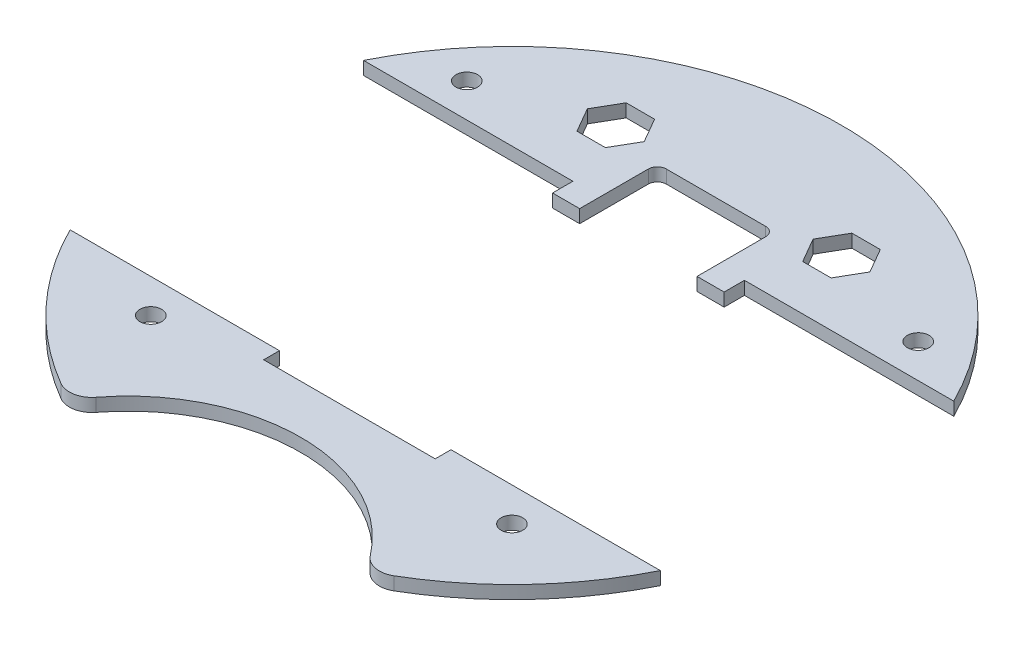
SolidWorks part; units mm, degrees
material "Acrylic (Medium-high impact)"
ref_plane "Front Plane" through (0, 0, 0) normal (0, 0, 1) x (1, 0, 0)
ref_plane "Top Plane" through (0, 0, 0) normal (0, 1, 0) x (1, 0, 0)
ref_plane "Right Plane" through (0, 0, 0) normal (1, 0, 0) x (0, 0, -1)
sketch "Sketch1" plane through (0, 0, 0) normal (0, 1, 0) x (1, 0, 0)
  line L0 (0, -85) -> (-32.7511, -65.2408) construction
  line L1 (0, -85) -> (0, 0) construction
  arc A0 (36.8566, -63.0126) -> (-36.8566, -63.0126) centre (0, 0) ccw
  arc A1 (30.3631, -61.7375) -> (-30.3631, -61.7375) centre (0, -85) ccw
  arc A2 (36.8566, -63.0126) -> (30.3631, -61.7375) centre (34.3322, -58.6967) cw
  arc A3 (-30.3631, -61.7375) -> (-36.8566, -63.0126) centre (-34.3322, -58.6967) cw
  dimension "D1" = 146
  dimension "D2" = 76.5
  dimension "D4" = 5
  dimension "D3" = 85
extrude "Boss-Extrude1" add sketch "Sketch1" along normal blind 2.9
sketch "solenoid placement" plane through (0, 2.9, 0) normal (0, 1, 0) x (1, 0, 0)
  line L4 (-19, -36) -> (19, -36)
  line L5 (-19, 28) -> (-19, -36)
  line L6 (19, 28) -> (-19, 28)
  line L7 (19, -36) -> (19, 28)
  line L8 (-19, -36) -> (19, -36)
  line L9 (-19, 28) -> (-19, -36)
  line L10 (19, 28) -> (-19, 28)
  line L11 (19, -36) -> (19, 28)
  dimension "D1" = 0
extrude "Cut-Extrude1" cut sketch "solenoid placement" against normal through all
sketch "Sketch5" plane through (0, 2.9, 0) normal (0, 1, 0) x (1, 0, 0)
  line L6 (-18.7069, 48) -> (-21.8534, 53.45)
  line L7 (-21.8534, 53.45) -> (-28.1466, 53.45)
  line L8 (-28.1466, 53.45) -> (-31.2931, 48)
  line L9 (-31.2931, 48) -> (-28.1466, 42.55)
  line L10 (-28.1466, 42.55) -> (-21.8534, 42.55)
  line L11 (-21.8534, 42.55) -> (-18.7069, 48)
  line L12 (-18.7069, 48) -> (-21.8534, 53.45)
  line L13 (-21.8534, 53.45) -> (-28.1466, 53.45)
  line L14 (-28.1466, 53.45) -> (-31.2931, 48)
  line L15 (-31.2931, 48) -> (-28.1466, 42.55)
  line L16 (-28.1466, 42.55) -> (-21.8534, 42.55)
  line L17 (-21.8534, 42.55) -> (-18.7069, 48)
  line L18 (18.7069, 48) -> (21.8534, 42.55)
  line L19 (21.8534, 53.45) -> (18.7069, 48)
  line L20 (28.1466, 53.45) -> (21.8534, 53.45)
  line L21 (31.2931, 48) -> (28.1466, 53.45)
  line L22 (28.1466, 42.55) -> (31.2931, 48)
  line L23 (21.8534, 42.55) -> (28.1466, 42.55)
  line L24 (18.7069, 48) -> (21.8534, 42.55)
  line L25 (21.8534, 53.45) -> (18.7069, 48)
  line L26 (28.1466, 53.45) -> (21.8534, 53.45)
  line L27 (31.2931, 48) -> (28.1466, 53.45)
  line L28 (28.1466, 42.55) -> (31.2931, 48)
  line L29 (21.8534, 42.55) -> (28.1466, 42.55)
  dimension "D1" = 0
  dimension "D2" = 0
extrude "Cut-Extrude5" cut sketch "Sketch5" against normal through all
sketch "Sketch6" plane through (0, 2.9, 0) normal (0, 1, 0) x (1, 0, 0)
  circle A1 centre (40, -40) radius 2.4
  circle A2 centre (40, -40) radius 2.4
  circle A3 centre (-40, -40) radius 2.4
  circle A4 centre (-40, -40) radius 2.4
  circle A5 centre (-50, 40) radius 2.4
  circle A6 centre (-50, 40) radius 2.4
  circle A7 centre (50, 40) radius 2.4
  circle A8 centre (50, 40) radius 2.4
  dimension "D1" = 0
  dimension "D2" = 0
  dimension "D3" = 0
  dimension "D4" = 0
extrude "Cut-Extrude6" cut sketch "Sketch6" against normal through all
sketch "Sketch3" plane through (0, 2.9, 0) normal (0, 1, 0) x (1, 0, 0)
  line L0 (-19, 28) -> (-19, 32.5)
  line L1 (73, -32.5) -> (-73, -32.5)
  line L2 (73, -32.5) -> (73, 32.5)
  line L3 (73, 32.5) -> (19, 32.5)
  line L4 (-73, -32.5) -> (-73, 32.5)
  line L5 (73, -32.5) -> (-73, 32.5) construction
  line L6 (73, 32.5) -> (-73, -32.5) construction
  line L7 (-19, 28) -> (19, 28)
  line L8 (19, 28) -> (19, 32.5)
  line L9 (-19, 32.5) -> (-73, 32.5)
  arc A0 (36.8566, -63.0126) -> (-36.8566, -63.0126) centre (0, 0) ccw construction
  point P0 (0, 0)
  dimension "D1" = 65
extrude "Cut-Extrude3" cut sketch "Sketch3" against normal through all
sketch "Sketch7" plane through (0, 2.9, 0) normal (0, 1, 0) x (1, 0, 0)
  line L4 (-13, 28) -> (13, 28)
  line L5 (13, 28) -> (13, 43.2)
  line L6 (11, 45.2) -> (-11, 45.2)
  line L7 (-13, 43.2) -> (-13, 28)
  line L8 (-13, 28) -> (13, 28)
  line L9 (13, 28) -> (13, 43.2)
  line L10 (11, 45.2) -> (-11, 45.2)
  line L11 (-13, 43.2) -> (-13, 28)
  arc A2 (13, 43.2) -> (11, 45.2) centre (11, 43.2) ccw
  arc A3 (-11, 45.2) -> (-13, 43.2) centre (-11, 43.2) ccw
  arc A4 (13, 43.2) -> (11, 45.2) centre (11, 43.2) ccw
  arc A5 (-11, 45.2) -> (-13, 43.2) centre (-11, 43.2) ccw
  dimension "D1" = 0
extrude "Cut-Extrude7" cut sketch "Sketch7" against normal through all
equation "\"smallPulleyTeeth\"= 15"
equation "\"largePulleyTeeth\"= 30"
equation "\"eighthThick\"= 2.9mm"
equation "\"sixteenthThick\"= 1.7mm"
equation "\"quarterThick\"=6.0mm"
equation "\"OD\"= 146mm"
equation "\"puckAngle\"= 60.5deg"
equation "\"D1@Sketch1\"=\"OD\""
equation "\"puckDiam\"= 76.5mm"
equation "\"D2@Sketch1\"=\"puckDiam\""
equation "\"D1@Boss-Extrude1\"=\"eighthThick\""
equation "\"axlePress\"= 5.9mm"
equation "\"press\"= 0.2mm"
equation "\"wheelClear\"= 0.3mm"
equation "\"10-32clear\"= 4.8mm"
equation "\"6-32clear\"= 3.3mm"
equation "\"8-32clear\"= 4.0mm"
equation "\"wheelHeight\"= 22mm"
equation "\"wheelWell\"= 65mm"
equation "\"D1@Sketch3\"=\"wheelWell\""
equation "\"puckDist\"= 85mm"
equation "\"scoopFillet\"= 5mm"
equation "\"4-40clear\"= 3.0mm"
equation "\"D3@Sketch1\"=\"puckDist\""
equation "\"D4@Sketch1\"=\"scoopFillet\""
